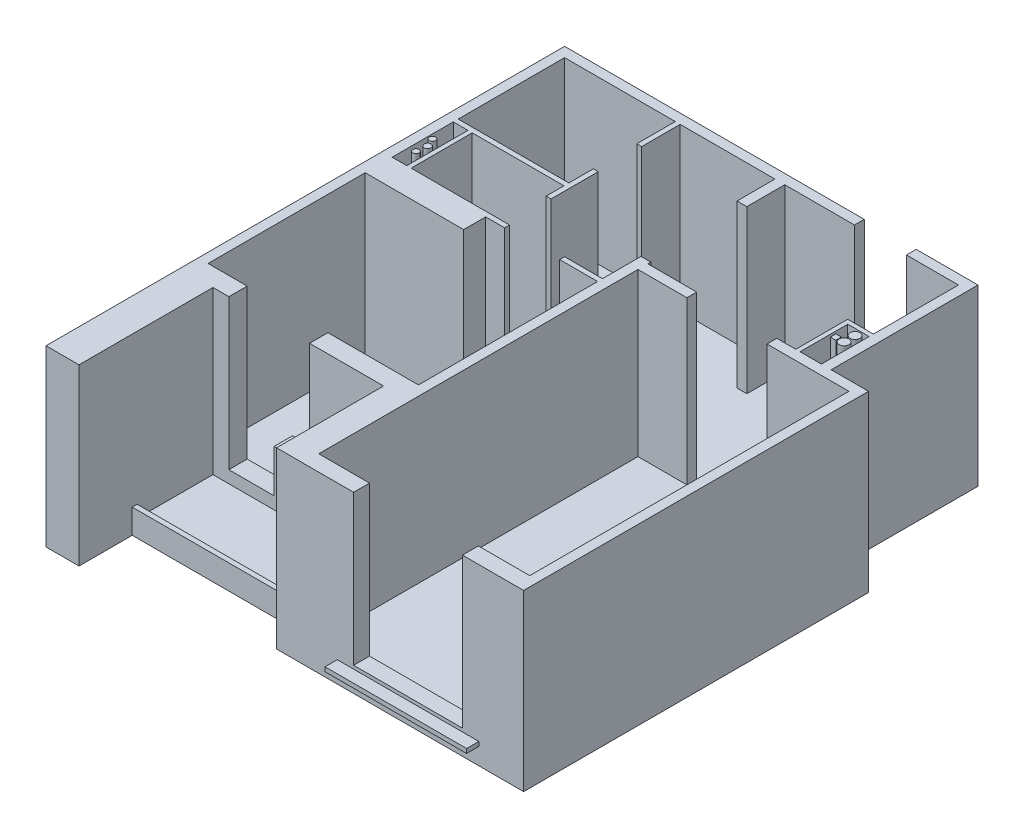
SolidWorks part; units mm, degrees
ref_plane "Спереди" through (0, 0, 0) normal (0, 0, 1) x (1, 0, 0)
ref_plane "Сверху" through (0, 0, 0) normal (0, 1, 0) x (1, 0, 0)
ref_plane "Справа" through (0, 0, 0) normal (1, 0, 0) x (0, 0, -1)
other "Configuration Table"
sketch "чертеж" plane through (0, 0, 0) normal (0, 1, 0) x (1, 0, 0)
  line L0 (-122.4645, -5934.5928) -> (200.8688, -5934.5928) construction
  line L1 (11.3792, -6202.3586) -> (334.7125, -6202.3586) construction
  line L2 (-29.7674, 42.6262) -> (294.8993, 42.6262) construction
  line L3 (-41.8231, 39.2884) -> (282.8435, 39.2884) construction
  line L4 (2418.4622, -1094.6493) -> (2743.1288, -1094.6493) construction
  line L5 (-60.4594, 42.9789) -> (264.2073, 42.9789) construction
  line L6 (-48.7728, 66.0913) -> (275.8939, 66.0913) construction
  line L7 (-42.5542, 93.9023) -> (282.1124, 93.9023) construction
  line L8 (134.2311, 87.3942) -> (458.8978, 87.3942) construction
  line L9 (-47.3906, 51.9395) -> (277.2761, 51.9395) construction
  line L10 (-66.0858, -48.647) -> (431.2475, -48.647) construction
sketch "Эскиз по чертежу" plane through (0, 0, 0) normal (0, 1, 0) x (1, 0, 0)
  line L0 (0, 0) -> (0, 8400) construction
  line L1 (0, 8400) -> (1925, 8400) construction
  line L2 (6600, 8400) -> (6600, 6000) construction
  line L4 (7200, 6000) -> (7200, 600) construction
  line L5 (7200, 600) -> (3600, 600) construction
  line L6 (3600, 600) -> (3600, 8400) construction
  line L7 (3600, 2400) -> (0, 2400) construction
  line L8 (3600, 5475) -> (0, 5475) construction
  line L32 (6600, 6000) -> (7200, 6000) construction
  line L33 (0, 870) -> (3600, 870) construction
  line L37 (0, 1050) -> (3600, 1050) construction
  line L40 (1925, 5475) -> (1925, 6550) construction
  line L42 (1925, 6550) -> (1925, 8400) construction
  line L45 (1925, 8400) -> (3600, 8400) construction
  line L46 (3600, 8400) -> (6600, 8400) construction
  line L49 (1925, 6550) -> (0, 6550) construction
  dimension "D1" = 600
  dimension "D2" = 1800
  dimension "D3" = 3600
  dimension "D4" = 1530
  dimension "D5" = 600
  dimension "D6" = 3600
  dimension "D7" = 3600
  dimension "D8" = 2400
  dimension "D9" = 2925
  dimension "D10" = 1925
  dimension "D11" = 1850
  dimension "D12" = 1350
sketch "Эскиз3" plane through (0, 0, 0) normal (0, 1, 0) x (1, 0, 0)
  line L1 (3520, 6130) -> (3680, 6130)
  line L2 (4510, 700) -> (4510, 1200) construction
  line L11 (80, 8320) -> (3520, 8320)
  line L15 (3520, 8320) -> (3520, 7700)
  line L16 (3520, 7700) -> (3680, 7700)
  line L17 (3680, 7700) -> (3680, 8320)
  line L20 (6520, 6080) -> (5790, 6080)
  line L21 (-80, 8480) -> (4820, 8480)
  line L22 (6520, 8320) -> (6520, 6080)
  line L24 (4820, 8480) -> (4820, 8320)
  line L25 (4820, 8320) -> (3680, 8320)
  line L26 (6680, 8480) -> (5670, 8480)
  line L29 (7130, 5920) -> (7130, 700)
  line L30 (4510, 700) -> (3680, 700)
  line L32 (6290, 540) -> (7290, 540)
  line L33 (7290, 540) -> (7290, 6080)
  line L34 (7290, 6080) -> (6680, 6080)
  line L35 (6680, 6080) -> (6680, 8480)
  line L39 (5670, 8480) -> (5670, 8320)
  line L40 (5670, 8320) -> (6520, 8320)
  line L41 (5790, 6080) -> (5790, 5920)
  line L42 (5790, 5920) -> (7130, 5920)
  line L45 (-80, 8480) -> (-80, 0)
  line L46 (-80, 0) -> (80, 0)
  line L47 (3680, 6080) -> (4480, 6080)
  line L52 (80, 0) -> (80, 8320)
  line L60 (3680, 700) -> (3680, 5920)
  line L68 (3520, 6130) -> (3520, 540)
  line L69 (4480, 6080) -> (4480, 5920)
  line L70 (4480, 5920) -> (3680, 5920)
  line L71 (7130, 700) -> (6290, 700)
  line L72 (6290, 540) -> (6290, 700)
  line L73 (3520, 540) -> (4510, 540)
  line L74 (4510, 540) -> (4510, 700)
  line L76 (4510, 1200) -> (3680, 1200) construction
  line L77 (6290, 700) -> (6290, 1200) construction
  line L78 (4510, 1200) -> (6290, 1200) construction
  line L79 (6290, 1200) -> (7130, 1200) construction
  line L80 (3680, 6130) -> (3680, 6080)
  line L81 (3600, 8400) -> (6600, 8400) construction
  line L83 (0, 0) -> (0, 8400) construction
  dimension "D1" = 3440
  dimension "D2" = 3450
  dimension "D3" = 5220
  dimension "D4" = 1340
  dimension "D5" = 160
  dimension "D6" = 2840
  dimension "D7" = 160
  dimension "D8" = 160
  dimension "D9" = 2240
  dimension "D10" = 160
  dimension "D11" = 80
  dimension "D12" = 160
  dimension "D13" = 160
  dimension "D14" = 80
  dimension "D15" = 1140
  dimension "D16" = 160
  dimension "D17" = 850
  dimension "D18" = 620
  dimension "D19" = 160
  dimension "D20" = 800
  dimension "D21" = 840
  dimension "D22" = 500
  dimension "D23" = 50
  dimension "D24" = 830
  dimension "D25" = 850
  dimension "D26" = 1310
  dimension "D27" = 730
  dimension "D28" = 1570
  dimension "D29" = 1780
extrude "несущие стены" add sketch "Эскиз3" along normal blind 2650 separate body
sketch "Эскиз8" plane through (0, 0, 0) normal (0, 1, 0) x (1, 0, 0)
  line L0 (80, 8320) -> (3520, 8320) construction
  line L1 (80, 5500) -> (1690, 5500)
  line L2 (80, 5500) -> (80, 5060)
  line L3 (80, 5060) -> (1690, 5060)
  line L4 (1690, 5500) -> (1690, 5060)
  line L10 (80, 0) -> (80, 8320) construction
  dimension "D1" = 440
  dimension "D2" = 2820
  dimension "D5" = 1610
extrude "вытяжка кухня" add sketch "Эскиз8" along normal up to surface (2650 mm away) up to face at (6481.4286, 2650, -5160)
sketch "Эскиз5" plane through (0, 0, 0) normal (0, 1, 0) x (1, 0, 0)
  line L0 (80, 6580) -> (1890, 6580)
  line L1 (1970, 6210) -> (1970, 5500) construction
  line L2 (1890, 6580) -> (1890, 6980)
  line L3 (1890, 6980) -> (1970, 6980)
  line L4 (1970, 6980) -> (1970, 6210)
  line L5 (1970, 6210) -> (1890, 6210)
  line L6 (1890, 6210) -> (1890, 6500)
  line L7 (1890, 6500) -> (80, 6500)
  line L9 (80, 6500) -> (80, 6580)
  line L10 (1690, 5420) -> (2000, 5420)
  line L12 (2000, 5420) -> (2000, 5500)
  line L17 (2000, 5500) -> (1690, 5500)
  line L18 (1690, 5500) -> (1690, 5420)
  line L19 (3520, 5420) -> (2900, 5420)
  line L20 (3520, 6130) -> (3520, 540) construction
  line L21 (2900, 5420) -> (2900, 5500)
  line L22 (2900, 5500) -> (3520, 5500)
  line L23 (80, 0) -> (80, 5060) construction
  line L24 (3520, 5500) -> (3520, 5420)
  line L25 (1890, 8320) -> (1890, 7690)
  line L26 (1690, 5060) -> (1690, 5500) construction
  line L27 (1890, 7690) -> (1970, 7690)
  line L28 (1970, 7690) -> (1970, 8320)
  line L30 (1970, 8320) -> (1890, 8320)
  line L31 (80, 8320) -> (3520, 8320) construction
  line L32 (3520, 8320) -> (3520, 7700) construction
  point P12 (2000, 5460)
  point P14 (2900, 5460)
  dimension "D1" = 630
  dimension "D2" = 1810
  dimension "D3" = 1550
  dimension "D4" = 1740
  dimension "D5" = 80
  dimension "D6" = 400
  dimension "D7" = 770
  dimension "D8" = 1000
  dimension "D9" = 310
  dimension "D10" = 30
  dimension "D11" = 80
  dimension "D12" = 80
  dimension "D13" = 710
  dimension "D14" = 290
  dimension "D15" = 620
  dimension "D16" = 900
  dimension "D17" = 710
extrude "перегородки санузла" add sketch "Эскиз5" along normal up to surface (2650 mm away) up to face at (1970, 2650, -6197.1429)
sketch "Эскиз9" plane through (0, 0, 0) normal (0, 1, 0) x (1, 0, 0)
  line L0 (320, 6500) -> (390, 6500)
  line L1 (6520, 6930) -> (6100, 6930)
  line L4 (6100, 6930) -> (6100, 6080)
  line L5 (80, 6500) -> (1890, 6500) construction
  line L6 (6520, 6080) -> (5790, 6080) construction
  line L7 (6170, 6860) -> (6520, 6860)
  line L8 (6170, 6860) -> (6170, 6080)
  line L11 (6520, 8320) -> (6520, 6080) construction
  line L13 (390, 5500) -> (320, 5500)
  line L14 (390, 6500) -> (390, 5500)
  line L15 (2000, 5500) -> (80, 5500) construction
  line L19 (320, 6500) -> (320, 5500)
  line L22 (1890, 6500) -> (1890, 6210) construction
  line L23 (5790, 6080) -> (5790, 5920) construction
  line L24 (6520, 6930) -> (6520, 6860)
  line L25 (6100, 6080) -> (6170, 6080)
  line L26 (6390, 6580) -> (6390, 6080) construction
  line L27 (6390, 6580) -> (6390, 6760) construction
  line L28 (6390, 6760) -> (6520, 6760) construction
  line L29 (6300, 6580) -> (6310, 6580) construction
  line L30 (6210, 6625) -> (6300, 6625)
  line L31 (6210, 6625) -> (6210, 6535)
  line L32 (6210, 6535) -> (6300, 6535)
  line L33 (190, 5780) -> (190, 5500) construction
  line L34 (150, 6090) -> (150, 6500) construction
  line L35 (150, 6090) -> (80, 6090) construction
  line L36 (190, 5780) -> (80, 5780) construction
  line L37 (80, 5500) -> (80, 6500) construction
  line L38 (210, 5950) -> (80, 5950) construction
  line L39 (210, 5950) -> (210, 5500) construction
  line L40 (6300, 6625) -> (6300, 6535)
  line L41 (5670, 8320) -> (6520, 8320) construction
  circle A0 centre (6390, 6760) radius 80
  circle A1 centre (6390, 6580) radius 80
  circle A2 centre (150, 6090) radius 50
  circle A3 centre (210, 5950) radius 55
  circle A4 centre (190, 5780) radius 50
  point P13 (6310, 6930)
  point P23 (6390, 6500)
  dimension "D5" = 130
  dimension "D10" = 310
  dimension "D12" = 100
  dimension "D15" = 110
  dimension "D16" = 110
  dimension "D9" = 160
  dimension "D1" = 850
  dimension "D2" = 70
  dimension "D3" = 310
  dimension "D4" = 420
  dimension "D6" = 500
  dimension "D7" = 680
  dimension "D8" = 70
  dimension "D11" = 1500
  dimension "D13" = 280
  dimension "D14" = 310
  dimension "D17" = 130
  dimension "D18" = 450
  dimension "D19" = 410
  dimension "D20" = 70
  dimension "D21" = 90
  dimension "D22" = 10
  dimension "D23" = 1390
extrude "зсс" add sketch "Эскиз9" along normal up to surface (2650 mm away) up to face at (6481.4286, 2650, -5160)
sketch "Эскиз7" plane through (0, 0, 0) normal (0, 1, 0) x (1, 0, 0)
  line L0 (80, 0) -> (80, 5060) construction
  line L1 (720, 2490) -> (80, 2490)
  line L2 (460, 2190) -> (460, 0)
  line L3 (3250, 2190) -> (3250, 440)
  line L4 (3250, 440) -> (4510, 440)
  line L5 (460, 0) -> (80, 0)
  line L6 (80, 2490) -> (80, 0)
  line L7 (80, 0) -> (80, 5060) construction
  line L8 (3250, 2190) -> (2040, 2190)
  line L9 (3520, 540) -> (4510, 540) construction
  line L10 (2040, 2490) -> (3520, 2490)
  line L19 (4510, 540) -> (4510, 440)
  line L20 (6290, 540) -> (7290, 540)
  line L21 (6290, 540) -> (6290, 440)
  line L22 (6290, 440) -> (7290, 440)
  line L23 (7290, 540) -> (7290, 440)
  line L24 (2040, 2190) -> (2040, 2490)
  line L25 (3520, 2490) -> (3520, 540)
  line L26 (3520, 540) -> (4510, 540)
  line L27 (3520, 5420) -> (3520, 540) construction
  line L28 (6290, 540) -> (7290, 540) construction
  line L29 (460, 2190) -> (720, 2190)
  line L30 (720, 2190) -> (720, 2490)
  line L31 (4510, 540) -> (4510, 700) construction
  line L32 (6290, 700) -> (6290, 540) construction
  line L34 (2900, 5420) -> (3520, 5420) construction
  line L35 (80, 5060) -> (1690, 5060) construction
  line L36 (3520, 5420) -> (3520, 540) construction
  point P31 (720, 2340)
  dimension "D1" = 2790
  dimension "D2" = 100
  dimension "D3" = 2930
  dimension "D4" = 2570
  dimension "D5" = 1480
  dimension "D6" = 1210
  dimension "D7" = 260
  dimension "D8" = 640
  dimension "D9" = 300
extrude "лоджия" add sketch "Эскиз7" along normal up to surface (2650 mm away) up to face at (1842.1429, 2650, -6505.7143)
sketch "Эскиз11" plane through (0, 0, 0) normal (0, 1, 0) x (1, 0, 0)
  line L1 (2040, 2490) -> (1460, 2490)
  line L2 (2040, 2490) -> (2040, 2190)
  line L3 (2040, 2190) -> (1460, 2190)
  line L4 (1460, 2490) -> (1460, 2190)
  line L5 (720, 2190) -> (720, 2490) construction
  dimension "D1" = 740
  dimension "D2" = 580
extrude "лоджияперегородка" add sketch "Эскиз11" along normal blind 900
sketch "Эскиз4" plane through (0, 0, 0) normal (0, 1, 0) x (1, 0, 0)
  line L8 (-80, 8480) -> (6680, 8480)
  line L9 (6680, 8480) -> (6680, 6080)
  line L10 (6680, 6080) -> (7290, 6080)
  line L11 (7290, 6080) -> (7290, 440)
  line L13 (3250, 440) -> (3250, 870)
  line L14 (3250, 870) -> (460, 870)
  line L17 (-80, 0) -> (-80, 8480)
  line L18 (6680, 6080) -> (6680, 8480) construction
  line L19 (6680, 8480) -> (5670, 8480) construction
  line L20 (460, 950) -> (3250, 950) construction
  line L21 (460, 0) -> (460, 2190) construction
  line L22 (3250, 2190) -> (3250, 440) construction
  line L24 (460, 870) -> (460, 0)
  line L25 (460, 0) -> (-80, 0)
  line L26 (3250, 440) -> (7290, 440)
  line L27 (2040, 2190) -> (3250, 2190) construction
  line L28 (460, 0) -> (460, 2190) construction
  line L29 (-80, 0) -> (460, 0) construction
  dimension "D1" = 80
  dimension "D2" = 1240
extrude "пол" add sketch "Эскиз4" against normal blind 200
sketch "Эскиз49" plane through (0, 0, 0) normal (0, 1, 0) x (1, 0, 0)
  line L0 (460, 0) -> (460, 2190) construction
  line L1 (3250, 870) -> (460, 870)
  line L2 (3250, 870) -> (3250, 950)
  line L3 (3250, 950) -> (460, 950)
  line L4 (460, 870) -> (460, 950)
  dimension "D1" = 80
extrude "лоджиябордюрподокно" add sketch "Эскиз49" along normal blind 200
sketch "Эскиз50" plane through (0, 0, -440) normal (0, 0, 1) x (1, 0, 0)
  line L0 (4510, 0) -> (6290, 0) construction
  line L1 (4242.5, 145) -> (6557.5, 145)
  line L2 (4242.5, 145) -> (4242.5, 75)
  line L3 (4242.5, 75) -> (6557.5, 75)
  line L4 (6557.5, 145) -> (6557.5, 75)
  line L5 (5400, 0) -> (5400, 75) construction
  point P4 (5400, 75)
  point P5 (5400, 0)
  dimension "D1" = 70
  dimension "D2" = 2315
  dimension "D3" = 75
sketch "Эскиз54" plane through (0, 0, 0) normal (0, 1, 0) x (1, 0, 0)
  line L1 (720, 2490) -> (1460, 2490)
  line L2 (720, 2490) -> (720, 2190)
  line L3 (720, 2190) -> (1460, 2190)
  line L4 (1460, 2490) -> (1460, 2190)
extrude "лоджиябордюрподдверь" add sketch "Эскиз54" along normal blind 200
sketch "Эскиз51" plane through (0, 0, 0) normal (0, 1, 0) x (1, 0, 0)
  line L0 (4510, 440) -> (4510, 700) construction
  line L1 (6290, 440) -> (4510, 440)
  line L2 (6290, 440) -> (6290, 700)
  line L3 (6290, 700) -> (4510, 700)
  line L4 (4510, 440) -> (4510, 700)
extrude "залбордярподконо" add sketch "Эскиз51" along normal blind 200
extrude "подоконникнаружний" add sketch "Эскиз50" along normal blind 200
sketch "Эскиз53" [suppressed] plane through (0, 2650, 0) normal (0, 1, 0) x (1, 0, 0)
  line L1 (2040, 2490) -> (720, 2490)
  line L2 (2040, 2490) -> (2040, 2190)
  line L3 (2040, 2190) -> (720, 2190)
  line L4 (720, 2490) -> (720, 2190)
extrude "лоджияверх" [suppressed] add sketch "Эскиз53" against normal blind 310
sketch "Эскиз52" [suppressed] plane through (0, 2650, 0) normal (0, 1, 0) x (1, 0, 0)
  line L1 (4510, 440) -> (6290, 440)
  line L2 (4510, 440) -> (4510, 700)
  line L3 (4510, 700) -> (6290, 700)
  line L4 (6290, 440) -> (6290, 700)
extrude "залокноверх" [suppressed] add sketch "Эскиз52" against normal blind 330
sketch "Эскиз55" [suppressed] plane through (0, 2650, 0) normal (0, 1, 0) x (1, 0, 0)
  line L1 (4820, 8480) -> (5670, 8480)
  line L2 (4820, 8480) -> (4820, 8320)
  line L3 (4820, 8320) -> (5670, 8320)
  line L4 (5670, 8480) -> (5670, 8320)
extrude "входнаядверьверх" [suppressed] add sketch "Эскиз55" against normal blind 570
sketch "Эскиз65" [suppressed] plane through (0, 2650, 0) normal (0, 1, 0) x (1, 0, 0)
  line L0 (2000, 5500) -> (390, 5500) construction
  line L1 (1890, 6210) -> (1970, 6210)
  line L2 (1890, 6210) -> (1890, 5500)
  line L3 (1890, 5500) -> (1970, 5500)
  line L4 (1970, 6210) -> (1970, 5500)
  line L6 (1890, 7690) -> (1970, 7690)
  line L7 (1890, 7690) -> (1890, 6980)
  line L8 (1890, 6980) -> (1970, 6980)
  line L9 (1970, 7690) -> (1970, 6980)
  line L10 (3520, 7700) -> (3680, 7700)
  line L11 (3520, 7700) -> (3520, 6130)
  line L12 (3520, 6130) -> (3680, 6130)
  line L13 (3680, 7700) -> (3680, 6130)
  line L14 (2000, 5500) -> (2900, 5500)
  line L15 (2000, 5500) -> (2000, 5420)
  line L16 (2000, 5420) -> (2900, 5420)
  line L17 (2900, 5500) -> (2900, 5420)
  line L18 (4480, 6080) -> (5790, 6080)
  line L19 (4480, 6080) -> (4480, 5920)
  line L20 (4480, 5920) -> (5790, 5920)
  line L21 (5790, 6080) -> (5790, 5920)
extrude "остальные" [suppressed] add sketch "Эскиз65" against normal offset from surface (550 mm away) 2100 up to face at (3285.8333, 0, -6273.75)
sketch "Эскиз73" plane through (0, 0, 0) normal (0, 1, 0) x (1, 0, 0)
  line L0 (3520, 2490) -> (80, 2490) construction
  line L1 (80, 5060) -> (1970, 5060)
  line L2 (80, 5060) -> (80, 2490)
  line L3 (80, 2490) -> (720, 2490)
  line L4 (720, 4460) -> (720, 2490)
  line L5 (80, 3090) -> (720, 3090) construction
  line L6 (3520, 2490) -> (2620, 2490)
  line L7 (3520, 2490) -> (3520, 4490)
  line L8 (3520, 4490) -> (2620, 4490)
  line L9 (2620, 2490) -> (2620, 4490)
  line L10 (80, 4460) -> (720, 4460) construction
  line L11 (1970, 5060) -> (1970, 4460)
  line L12 (1872.0394, 3492.1247) -> (2472.0394, 3492.1247)
  line L13 (1872.0394, 3492.1247) -> (1872.0394, 2492.1247)
  line L14 (1872.0394, 2492.1247) -> (2472.0394, 2492.1247)
  line L15 (2472.0394, 3492.1247) -> (2472.0394, 2492.1247)
  line L16 (1970, 4460) -> (720, 4460)
  line L17 (1970, 6210) -> (1970, 5060) construction
  line L20 (720, 4460) -> (720, 5060) construction
  line L21 (1370, 4460) -> (1370, 5060) construction
  line L23 (121.4231, 3440) -> (671.4231, 3440)
  line L24 (121.4231, 3440) -> (121.4231, 3140)
  line L25 (121.4231, 3140) -> (671.4231, 3140)
  line L26 (671.4231, 3440) -> (671.4231, 3140)
  line L27 (176.255, 4410) -> (626.255, 4410)
  line L28 (176.255, 4410) -> (176.255, 3960)
  line L29 (176.255, 3960) -> (626.255, 3960)
  line L30 (626.255, 4410) -> (626.255, 3960)
  dimension "D2" = 900
  dimension "D3" = 2000
  dimension "D4" = 600
  dimension "D5" = 600
  dimension "D6" = 50
  dimension "D7" = 1000
  dimension "D8" = 600
  dimension "D10" = 600
  dimension "D12" = 550
  dimension "D13" = 300
  dimension "D14" = 50
  dimension "D15" = 520
  dimension "D16" = 650
  dimension "D17" = 450
  dimension "D18" = 450
sketch "Эскиз47" [suppressed] plane through (0, 0, 0) normal (0, 1, 0) x (1, 0, 0)
  line L0 (3520, 5420) -> (3520, 2490) construction
  line L1 (1690, 6500) -> (3520, 6500) construction
  line L2 (1690, 6500) -> (1690, 4300) construction
  line L3 (1690, 4300) -> (3520, 4300) construction
  line L4 (3520, 6500) -> (3520, 4300) construction
  line L5 (1610, 5060) -> (1610, 6580) construction
  line L6 (390, 6500) -> (1890, 6500) construction
  line L7 (1690, 5060) -> (1690, 5420) construction
  line L9 (1970, 7720) -> (1970, 8320) construction
  line L10 (1890, 6580) -> (80, 6580) construction
  line L11 (1890, 8320) -> (1970, 8320)
  line L12 (1890, 8320) -> (1890, 6580)
  line L13 (1610, 6580) -> (1690, 6580) construction
  line L14 (1690, 6580) -> (1690, 6500) construction
  line L15 (1890, 6580) -> (1970, 6580)
  line L16 (1970, 8320) -> (1970, 6580)
  line L17 (3520, 5420) -> (3520, 2490) construction
  line L18 (3520, 3790) -> (3680, 3790)
  line L19 (3520, 3790) -> (3520, 3090)
  line L20 (3520, 3090) -> (3680, 3090)
  line L21 (3680, 3790) -> (3680, 3090)
  line L22 (3680, 700) -> (3680, 5920) construction
  line L23 (1890, 7020) -> (1890, 6580) construction
  line L24 (3520, 2490) -> (80, 2490) construction
  line L25 (1970, 6200) -> (1970, 7020) construction
  line L26 (390, 6500) -> (1610, 6500)
  line L27 (390, 6500) -> (390, 6580)
  line L28 (390, 6580) -> (1610, 6580)
  line L29 (1610, 6500) -> (1610, 6580)
  line L30 (3520, 5500) -> (1690, 5500)
  line L31 (3520, 5500) -> (3520, 5420)
  line L32 (3520, 5420) -> (1690, 5420)
  line L33 (1690, 5500) -> (1690, 5420)
  line L34 (1890, 6500) -> (1970, 6500)
  line L35 (1890, 6500) -> (1890, 6200)
  line L36 (1890, 6200) -> (1970, 6200)
  line L37 (1970, 6500) -> (1970, 6200)
  line L38 (1970, 5500) -> (1970, 8320) construction
  line L39 (80, 5060) -> (1690, 5060) construction
  dimension "D1" = 700
  dimension "D2" = 2200
  dimension "D3" = 600
extrude "Вырез-Вытянуть3" [suppressed] cut sketch "Эскиз47" along normal blind 2000
sketch "Эскиз48" [suppressed] plane through (0, 0, 0) normal (0, 1, 0) x (1, 0, 0)
  line L0 (5830, 5920) -> (7130, 5920) construction
  line L1 (1610, 6500) -> (1690, 6500)
  line L2 (1610, 6500) -> (1610, 5500)
  line L3 (1610, 5500) -> (1690, 5500)
  line L4 (1690, 6500) -> (1690, 5500)
  line L5 (5830, 6080) -> (5395, 6080)
  line L6 (5830, 6080) -> (5830, 5920)
  line L7 (5830, 5920) -> (5395, 5920)
  line L8 (5395, 6080) -> (5395, 5920)
  line L10 (3520, 6130) -> (3520, 3790) construction
  line L11 (3680, 6580) -> (3680, 6130)
  line L12 (1970, 6500) -> (3520, 6500)
  line L13 (3520, 6500) -> (3520, 6130)
  line L14 (3520, 6130) -> (3680, 6130)
  line L15 (3520, 6080) -> (3520, 3790) construction
  line L16 (3680, 6080) -> (3680, 6130) construction
  line L17 (3680, 700) -> (3680, 5920) construction
  line L18 (1970, 6500) -> (1970, 6580)
  line L19 (3680, 7720) -> (3520, 7720)
  line L20 (3520, 7720) -> (3520, 7280)
  line L21 (3520, 7280) -> (3680, 7280)
  line L22 (3680, 7280) -> (3680, 7720)
  line L23 (3680, 6580) -> (1970, 6580)
  line L24 (3680, 3790) -> (3520, 3790) construction
  line L25 (3680, 4040) -> (5330, 4040) construction
  line L26 (3680, 4040) -> (3680, 3940) construction
  line L27 (3680, 3940) -> (5330, 3940) construction
  line L28 (5330, 4040) -> (5330, 3940) construction
  line L29 (7130, 5920) -> (7130, 700) construction
  line L30 (5395, 8320) -> (5395, 6080) construction
  line L31 (4530, 5920) -> (4530, 6080) construction
  line L32 (3520, 6130) -> (3520, 3790) construction
  dimension "D1" = 865
  dimension "D2" = 700
  dimension "D3" = 100
  dimension "D4" = 150
  dimension "D5" = 1800
extrude "Бобышка-Вытянуть34" [suppressed] add sketch "Эскиз48" along normal through all
sketch "Эскиз60" [suppressed] plane through (0, 0, 0) normal (0, 1, 0) x (1, 0, 0)
  line L0 (1610, 5500) -> (390, 5500) construction
  line L1 (390, 6580) -> (550, 6580)
  line L2 (390, 6580) -> (390, 5500)
  line L3 (390, 5500) -> (550, 5500)
  line L4 (550, 6580) -> (550, 5500)
  line L5 (390, 5500) -> (390, 6580) construction
  dimension "D1" = 160
extrude "утолщениедлядуша" [suppressed] add sketch "Эскиз60" along normal up to surface (2640 mm away) up to face at (6433.75, 2650, -5368.75)
sketch "Эскиз61" [suppressed] plane through (0, 0, 0) normal (0, 1, 0) x (1, 0, 0)
  line L0 (1890, 6580) -> (80, 6580) construction
  line L1 (1890, 8320) -> (1970, 8320)
  line L2 (1890, 8320) -> (1890, 6580)
  line L3 (1890, 6210) -> (1970, 6210)
  line L4 (1970, 8320) -> (1970, 6210)
  line L5 (3520, 5500) -> (1690, 5500)
  line L6 (3520, 5500) -> (3520, 5420)
  line L7 (3520, 5420) -> (1690, 5420)
  line L8 (1690, 5500) -> (1690, 5420)
  line L9 (390, 6500) -> (1890, 6500)
  line L10 (390, 6500) -> (390, 6580)
  line L11 (390, 6580) -> (1890, 6580)
  line L13 (1890, 6500) -> (1890, 6210)
extrude "Вырез-Вытянуть4" [suppressed] cut sketch "Эскиз61" along normal up to surface (2640 mm away) up to face at (6433.75, 2650, -5368.75)
sketch "Эскиз62" [suppressed] plane through (0, 0, 0) normal (0, 1, 0) x (1, 0, 0)
  line L0 (7130, 5920) -> (7130, 700) construction
  line L1 (5130, 2900) -> (7130, 2900)
  line L2 (5130, 2900) -> (5130, 1400)
  line L3 (5130, 1400) -> (7130, 1400)
  line L4 (7130, 2900) -> (7130, 1400)
  line L5 (5790, 5920) -> (7130, 5920) construction
  line L9 (3680, 5920) -> (4480, 5920)
  line L11 (4680, 3600) -> (4680, 3680)
  line L12 (3680, 3680) -> (3880, 3680)
  line L13 (3680, 700) -> (3680, 5920) construction
  line L14 (7130, 1400) -> (7130, 700) construction
  line L15 (3880, 3680) -> (3880, 3600)
  line L16 (3880, 3600) -> (3680, 3600)
  line L17 (3680, 700) -> (3680, 5920) construction
  line L18 (3680, 3600) -> (3680, 3680)
  line L19 (4680, 3680) -> (4880, 3680)
  line L20 (4880, 3680) -> (4880, 4600)
  line L22 (7130, 4600) -> (7130, 4520)
  line L23 (7130, 5920) -> (7130, 700) construction
  line L24 (7130, 4520) -> (4960, 4520)
  line L25 (4960, 4520) -> (4960, 3600)
  line L26 (4680, 3600) -> (4960, 3600)
  line L27 (4960, 3600) -> (7130, 3600) construction
  line L28 (4880, 3680) -> (4960, 3680) construction
  line L29 (7130, 3600) -> (7130, 2900) construction
  line L30 (3680, 5920) -> (3680, 6080)
  line L31 (3880, 3600) -> (4680, 3600) construction
  line L32 (7130, 4600) -> (4880, 4600)
  line L36 (7130, 5920) -> (7130, 4600) construction
  line L37 (5790, 5920) -> (7130, 5920) construction
  line L38 (3680, 3680) -> (3680, 4480)
  line L39 (3680, 4480) -> (3520, 4480)
  line L40 (3520, 6130) -> (3520, 2490) construction
  line L41 (3520, 4480) -> (3520, 3680)
  line L42 (3520, 6130) -> (3520, 2490) construction
  line L43 (3520, 3680) -> (3680, 3680)
  line L44 (3680, 6080) -> (4480, 6080)
  line L45 (4480, 5920) -> (4480, 6080)
  line L46 (7130, 4650) -> (6330, 4650)
  line L47 (7130, 4650) -> (7130, 5920)
  line L48 (7130, 5920) -> (6330, 5920)
  line L49 (6330, 4650) -> (6330, 5920)
  line L50 (3520, 8320) -> (3520, 7700) construction
  line L55 (3680, 7150) -> (1690, 7150)
  line L57 (3680, 7700) -> (3680, 7150)
  line L58 (1690, 5500) -> (1540, 5500)
  line L60 (1540, 7300) -> (3520, 7300)
  line L61 (3520, 7300) -> (3520, 7700)
  line L62 (3520, 7300) -> (3520, 7150) construction
  line L63 (3520, 7700) -> (3680, 7700)
  line L64 (80, 8320) -> (3520, 8320) construction
  line L65 (1690, 5060) -> (1690, 5500) construction
  line L66 (1690, 5060) -> (1690, 5500) construction
  line L67 (1690, 5500) -> (390, 5500) construction
  line L69 (1690, 7150) -> (1690, 7000)
  line L70 (1690, 7000) -> (1540, 7000)
  line L71 (1540, 7000) -> (1540, 7300)
  line L72 (1690, 5500) -> (1690, 6200)
  line L73 (1690, 6200) -> (1540, 6200)
  line L74 (1540, 6200) -> (1540, 5500)
  line L75 (3520, 4980) -> (2490, 4980)
  line L76 (3520, 6130) -> (3220, 6130)
  line L77 (3520, 6130) -> (3520, 5530)
  line L78 (3520, 5530) -> (3220, 5530)
  line L79 (3220, 6130) -> (3220, 5530)
  line L80 (2490, 4980) -> (2490, 6130)
  line L81 (2490, 6130) -> (3210, 6130)
  line L82 (3210, 6130) -> (3210, 5520)
  line L83 (3210, 5520) -> (3520, 5520)
  line L84 (3520, 5520) -> (3520, 4980)
  line L85 (3210, 6130) -> (3220, 6130) construction
  line L86 (3520, 5520) -> (3520, 5530) construction
  line L88 (80, 5060) -> (680, 5060)
  line L89 (80, 5060) -> (80, 3860)
  line L90 (80, 3860) -> (680, 3860)
  line L91 (680, 5060) -> (680, 3860)
  point P72 (1615, 6200)
  dimension "D12" = 300
  dimension "D1" = 2000
  dimension "D2" = 1500
  dimension "D3" = 700
  dimension "D4" = 800
  dimension "D5" = 80
  dimension "D6" = 200
  dimension "D7" = 1320
  dimension "D8" = 920
  dimension "D9" = 700
  dimension "D10" = 200
  dimension "D11" = 800
  dimension "D13" = 1020
  dimension "D14" = 150
  dimension "D15" = 800
  dimension "D16" = 50
  dimension "D17" = 800
  dimension "D18" = 150
  dimension "D19" = 600
  dimension "D20" = 500
  dimension "D21" = 10
  dimension "D22" = 800
  dimension "D23" = 600
  dimension "D24" = 1200
sketch "Эскиз63" [suppressed] plane through (0, 0, 0) normal (0, 1, 0) x (1, 0, 0)
  line L1 (3680, 5920) -> (4480, 5920)
  line L2 (3680, 5920) -> (3680, 6080)
  line L3 (3680, 6080) -> (4480, 6080)
  line L4 (4480, 5920) -> (4480, 6080)
  line L5 (3680, 3680) -> (3520, 3680)
  line L6 (3680, 3680) -> (3680, 4480)
  line L7 (3680, 4480) -> (3520, 4480)
  line L8 (3520, 3680) -> (3520, 4480)
extrude "Вырез-Вытянуть6" [suppressed] cut sketch "Эскиз63" along normal through all
sketch "Эскиз64" [suppressed] plane through (0, 0, 0) normal (0, 1, 0) x (1, 0, 0)
  line L0 (4680, 3600) -> (4960, 3600)
  line L1 (3680, 3600) -> (3880, 3600)
  line L2 (3680, 3600) -> (3680, 3680)
  line L3 (3680, 3680) -> (3880, 3680)
  line L4 (3880, 3600) -> (3880, 3680)
  line L5 (4960, 3600) -> (4960, 4520)
  line L6 (4960, 4520) -> (7130, 4520)
  line L7 (7130, 4520) -> (7130, 4600)
  line L8 (7130, 4600) -> (4880, 4600)
  line L9 (4880, 4600) -> (4880, 3680)
  line L10 (4880, 3680) -> (4680, 3680)
  line L11 (4680, 3680) -> (4680, 3600)
extrude "Бобышка-Вытянуть35" [suppressed] add sketch "Эскиз64" along normal through all
sketch "Эскиз66" [suppressed] plane through (0, 0, 0) normal (0, 1, 0) x (1, 0, 0)
  line L1 (1890, 6500) -> (1970, 6500)
  line L2 (1890, 6500) -> (1890, 6210)
  line L3 (1890, 6210) -> (1970, 6210)
  line L4 (1970, 6500) -> (1970, 6210)
  line L5 (2900, 5500) -> (3520, 5500)
  line L6 (2900, 5500) -> (2900, 5420)
  line L7 (2900, 5420) -> (3520, 5420)
  line L8 (3520, 5500) -> (3520, 5420)
extrude "Вырез-Вытянуть7" [suppressed] cut sketch "Эскиз66" along normal blind 2100
sketch "Эскиз69" [suppressed] plane through (0, 0, 0) normal (0, 1, 0) x (1, 0, 0)
  line L1 (3520, 5420) -> (1970, 5420)
  line L2 (3520, 5420) -> (3520, 5500)
  line L3 (3520, 5500) -> (1970, 5500)
  line L4 (1970, 5420) -> (1970, 5500)
extrude "Вырез-Вытянуть9" [suppressed] cut sketch "Эскиз69" along normal through all
sketch "Эскиз68" [suppressed] plane through (0, 0, 0) normal (0, 1, 0) x (1, 0, 0)
  line L0 (2920, 6980) -> (2920, 6900)
  line L1 (3680, 6130) -> (3520, 6130)
  line L2 (3680, 6130) -> (3680, 6980)
  line L3 (3680, 6980) -> (2920, 6980)
  line L4 (3520, 6130) -> (3520, 6900)
  line L5 (2920, 6900) -> (3520, 6900)
  line L6 (3520, 8320) -> (3520, 2490) construction
  line L9 (1970, 6980) -> (2920, 6980) construction
  dimension "D1" = 600
  dimension "D2" = 80
extrude "Бобышка-Вытянуть36" [suppressed] add sketch "Эскиз68" along normal up to surface (2650 mm away) up to face at (6433.75, 2650, -5368.75)
sketch "Эскиз67" [suppressed] plane through (0, 0, 0) normal (0, 1, 0) x (1, 0, 0)
  line L0 (3520, 6900) -> (3520, 2490) construction
  line L1 (440, 5522.7398) -> (990, 5522.7398)
  line L2 (440, 5522.7398) -> (440, 5972.7398)
  line L3 (440, 5972.7398) -> (990, 5972.7398)
  line L4 (990, 5522.7398) -> (990, 5972.7398)
  line L6 (1023.4102, 6479.7499) -> (1573.4102, 6479.7499)
  line L7 (1023.4102, 6479.7499) -> (1023.4102, 6029.7499)
  line L8 (1023.4102, 6029.7499) -> (1573.4102, 6029.7499)
  line L9 (1573.4102, 6479.7499) -> (1573.4102, 6029.7499)
  line L10 (390, 5500) -> (990, 5500)
  line L11 (390, 5500) -> (390, 6500)
  line L12 (390, 6500) -> (1970, 6500)
  line L13 (990, 5500) -> (990, 6000)
  line L14 (1970, 6500) -> (1970, 6000)
  line L15 (2920, 6900) -> (3520, 6900)
  line L16 (1970, 6000) -> (990, 6000)
  line L17 (2920, 6900) -> (2920, 6300)
  line L18 (3520, 8320) -> (3520, 6980) construction
  line L19 (2920, 6900) -> (3520, 6900)
  line L20 (2920, 6900) -> (2920, 4500)
  line L21 (2920, 4500) -> (3520, 4500)
  line L22 (3520, 6900) -> (3520, 4500)
  line L23 (2920, 6300) -> (3520, 6300)
  line L24 (3520, 6900) -> (3520, 6300)
  line L25 (3520, 5456.8348) -> (2970, 5456.8348)
  line L26 (3520, 5456.8348) -> (3520, 5156.8348)
  line L27 (3520, 5156.8348) -> (2970, 5156.8348)
  line L28 (2970, 5456.8348) -> (2970, 5156.8348)
  line L29 (3520, 4500) -> (2920, 4500)
  line L30 (3520, 4500) -> (3520, 5100)
  line L31 (3520, 5100) -> (2920, 5100)
  line L32 (2920, 4500) -> (2920, 5100)
  line L33 (2620, 4490) -> (3520, 4490)
  line L34 (902.1854, 4035.485) -> (1502.1854, 4035.485)
  line L35 (902.1854, 4035.485) -> (902.1854, 3035.485)
  line L36 (902.1854, 3035.485) -> (1502.1854, 3035.485)
  line L37 (1502.1854, 4035.485) -> (1502.1854, 3035.485)
  line L38 (2620, 4490) -> (2620, 2490)
  line L39 (2620, 2490) -> (3520, 2490)
  line L40 (3520, 4490) -> (3520, 2490)
  line L41 (2920, 6900) -> (3520, 6900) construction
  line L46 (1346.4078, 3766.5226) -> (1796.4078, 3766.5226)
  line L51 (630.0751, 3770.9808) -> (1080.0751, 3770.9808)
  line L52 (630.0751, 3770.9808) -> (630.0751, 3320.9808)
  line L53 (630.0751, 3320.9808) -> (1080.0751, 3320.9808)
  line L54 (1080.0751, 3770.9808) -> (1080.0751, 3320.9808)
  line L55 (1346.4078, 3766.5226) -> (1346.4078, 3316.5226)
  line L56 (1346.4078, 3316.5226) -> (1796.4078, 3316.5226)
  line L57 (1796.4078, 3766.5226) -> (1796.4078, 3316.5226)
  dimension "D2" = 550
  dimension "D3" = 450
  dimension "D4" = 550
  dimension "D5" = 600
  dimension "D6" = 500
  dimension "D7" = 600
  dimension "D8" = 600
  dimension "D9" = 550
  dimension "D10" = 300
  dimension "D11" = 600
  dimension "D12" = 1200
  dimension "D13" = 1000
  dimension "D14" = 600
  dimension "D15" = 2000
  dimension "D16" = 900
  dimension "D17" = 450
  dimension "D19" = 450
  dimension "D20" = 450
sketch "Эскиз70" [suppressed] plane through (0, 0, 0) normal (0, 1, 0) x (1, 0, 0)
  line L0 (1890, 8320) -> (1890, 7690) construction
  line L1 (1970, 5500) -> (3520, 5500)
  line L2 (1970, 5500) -> (1970, 5420)
  line L3 (1970, 5420) -> (3520, 5420)
  line L4 (3520, 5500) -> (3520, 5420)
  line L5 (390, 6500) -> (1890, 6500)
  line L6 (390, 6500) -> (390, 6580)
  line L7 (390, 6580) -> (1890, 6580)
  line L8 (1890, 6500) -> (1890, 6580)
  line L9 (1970, 6980) -> (1890, 6980)
  line L10 (1970, 6980) -> (1970, 8320)
  line L11 (1970, 8320) -> (1890, 8320)
  line L12 (1890, 6980) -> (1890, 8320)
  line L13 (80, 8320) -> (1890, 8320) construction
extrude "Вырез-Вытянуть10" [suppressed] cut sketch "Эскиз70" along normal through all
sketch "Эскиз71" [suppressed] plane through (0, 0, 0) normal (0, 1, 0) x (1, 0, 0)
  line L0 (80, 6580) -> (80, 8320) construction
  line L1 (1890, 6980) -> (80, 6980)
  line L2 (1890, 6980) -> (1890, 6900)
  line L3 (1890, 6900) -> (80, 6900)
  line L4 (80, 6980) -> (80, 6900)
  line L5 (1890, 6980) -> (1970, 6980) construction
extrude "Бобышка-Вытянуть37" [suppressed] add sketch "Эскиз71" along normal up to surface (2650 mm away) up to face at (6433.75, 2650, -5368.75)
sketch "Эскиз72" [suppressed] plane through (0, 0, 0) normal (0, 1, 0) x (1, 0, 0)
  line L0 (3520, 8320) -> (3520, 2490) construction
  line L1 (80, 8320) -> (3520, 8320)
  line L2 (80, 8320) -> (80, 7720)
  line L3 (80, 7720) -> (3520, 7720)
  line L4 (3520, 8320) -> (3520, 7720)
  line L5 (80, 6980) -> (1970, 6980) construction
  line L6 (680, 8320) -> (680, 7720) construction
  line L7 (2920, 8320) -> (2920, 7720) construction
  line L9 (1970, 5420) -> (1970, 6980) construction
  dimension "D1" = 600
  dimension "D2" = 740
  dimension "D3" = 3440
  dimension "D4" = 600
  dimension "D5" = 600
  dimension "D6" = 1550
